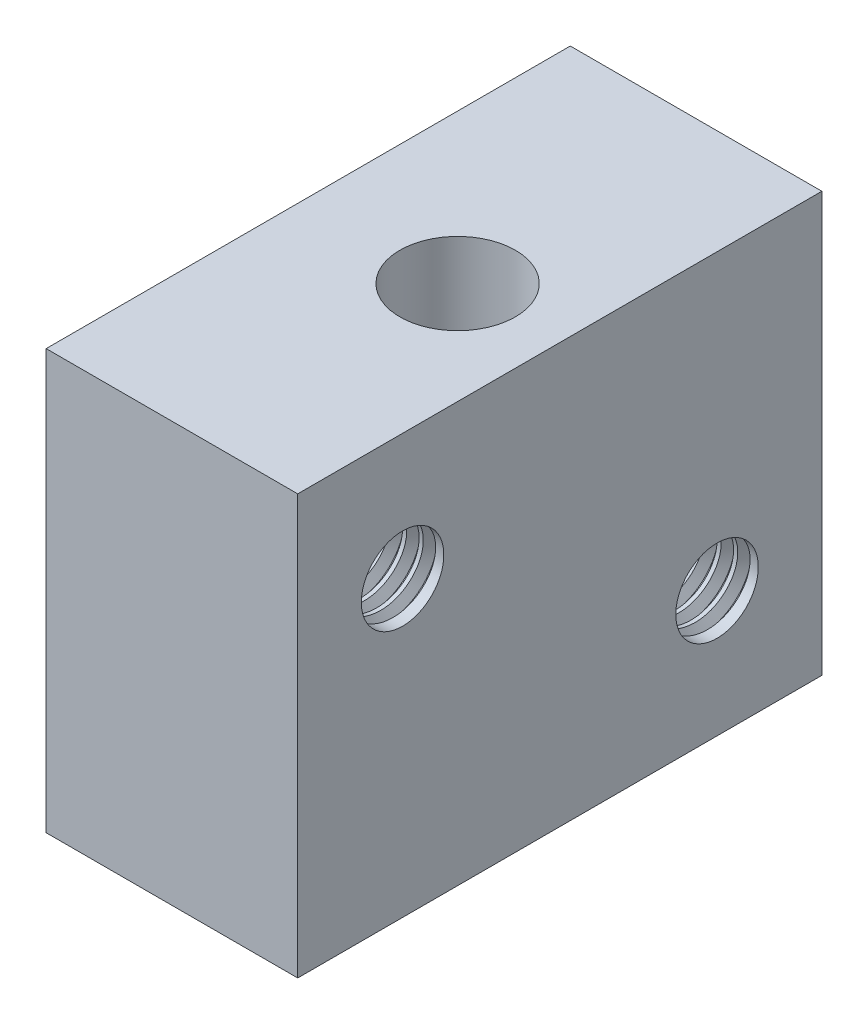
SolidWorks part; units mm, degrees
material "6061-T6 (SS)"
ref_plane "Front Plane" through (0, 0, 0) normal (1, 0, 0) x (0, 1, 0)
ref_plane "Top Plane" through (0, 0, 0) normal (0, 0, 1) x (0, 1, 0)
ref_plane "Right Plane" through (0, 0, 0) normal (0, 1, 0) x (-1, 0, 0)
sketch "Sketch1" plane through (0, 0, 0) normal (1, 0, 0) x (0, 1, 0)
  line L1 (6.35, -7.9375) -> (-6.35, -7.9375)
  line L2 (6.35, -7.9375) -> (6.35, 7.9375)
  line L3 (6.35, 7.9375) -> (-6.35, 7.9375)
  line L4 (-6.35, -7.9375) -> (-6.35, 7.9375)
  line L5 (6.35, -7.9375) -> (-6.35, 7.9375) construction
  line L6 (6.35, 7.9375) -> (-6.35, -7.9375) construction
  point P0 (0, 0)
  dimension "D1" = 15.875
  dimension "D2" = 12.7
extrude "Boss-Extrude1" add sketch "Sketch1" along normal blind 7.62
sketch "Sketch3" plane through (0, -6.35, 0) normal (0, -1, 0) x (1, 0, 0)
  line L10 (0, 7.9375) -> (0, -7.9375)
  line L11 (0, -7.9375) -> (7.62, -7.9375)
  line L12 (7.62, -7.9375) -> (7.62, 7.9375)
  line L13 (7.62, 7.9375) -> (0, 7.9375)
  line L14 (0, 7.9375) -> (0, -7.9375)
  line L15 (0, -7.9375) -> (7.62, -7.9375)
  line L16 (7.62, -7.9375) -> (7.62, 7.9375)
  line L17 (7.62, 7.9375) -> (0, 7.9375)
  circle A0 centre (4.525, 0) radius 1.75
  circle A1 centre (4.525, 0) radius 5 construction
  circle A2 centre (4.525, 0) radius 3 construction
  point P2 (9.525, 0)
  point P3 (2.775, 0)
  point P6 (-6.35, 0)
  dimension "D1" = 3.5
  dimension "D2" = 10
  dimension "D6" = 6
  dimension "D3" = 15.875
  dimension "D4" = 6.35
  dimension "D5" = 0
extrude "Cut-Extrude1" cut sketch "Sketch3" against normal blind 22.2885 contours A0 region at (4.525, -6.35, 0)
sketch "Sketch4" plane through (7.62, 0, 0) normal (1, 0, 0) x (0, 1, 0)
  line L0 (-6.35, 7.9375) -> (-6.35, -7.9375) construction
  line L1 (2.54, -4.7625) -> (-2.54, -4.7625) construction
  line L2 (2.54, -4.7625) -> (2.54, 4.7625) construction
  line L3 (2.54, 4.7625) -> (-2.54, 4.7625) construction
  line L4 (-2.54, -4.7625) -> (-2.54, 4.7625) construction
  line L5 (2.54, -4.7625) -> (-2.54, 4.7625) construction
  line L6 (2.54, 4.7625) -> (-2.54, -4.7625) construction
  line L7 (6.35, 7.9375) -> (-6.35, 7.9375) construction
  circle A3 centre (2.54, 4.7625) radius 1.25
  circle A4 centre (-2.54, -4.7625) radius 1.25
  point P0 (0, 0)
  dimension "D3" = 2.5
  dimension "D1" = 3.81
  dimension "D2" = 3.175
extrude "Cut-Extrude2" cut sketch "Sketch4" against normal blind 22.2885 contours A4 | A3 region at (7.62, 2.54, 4.7625) region at (7.62, -2.54, -4.7625)
thread "Thread2" pitch 0.5 method cut profile "Thread Profile2" start angle 0, offset 0, length 0, pitch 0.5, diameter 2.5
ref_plane "Plane2" through (7.62, 2.54, 6.0125) normal (0, -1, 0) x (0, 0, 1)
sketch "Thread Profile2" plane through (7.62, 2.54, 6.0125) normal (0, -1, 0) x (0, 0, 1)
  line L0 (0, 0) -> (0, 0.5) construction
  line L1 (0, 0) -> (0.2706, 0.1562)
  line L2 (0.2706, 0.1562) -> (0.2706, 0.2187)
  line L3 (0.2706, 0.2187) -> (0, 0.375)
  line L4 (0.2706, 0.1875) -> (0, 0.1875) construction
  line L11 (0, 0) -> (0, 0.375)
  point P2 (0, 0)
  dimension "Pitch" = 0.5
  dimension "Profile_Angle" = 60
  dimension "Profile_Land" = 0.0625
  dimension "Profile_Height" = 0.2706
thread "Thread3" pitch 0.5 method cut profile "Thread Profile3" start angle 0, offset 0, length 0, pitch 0.5, diameter 2.5
ref_plane "Plane3" through (7.62, -2.54, -3.5125) normal (0, -1, 0) x (0, 0, 1)
sketch "Thread Profile3" plane through (7.62, -2.54, -3.5125) normal (0, -1, 0) x (0, 0, 1)
  line L0 (0, 0) -> (0, 0.5) construction
  line L1 (0, 0) -> (0.2706, 0.1562)
  line L2 (0.2706, 0.1562) -> (0.2706, 0.2187)
  line L3 (0.2706, 0.2187) -> (0, 0.375)
  line L4 (0.2706, 0.1875) -> (0, 0.1875) construction
  line L11 (0, 0) -> (0, 0.375)
  point P2 (0, 0)
  dimension "Pitch" = 0.5
  dimension "Profile_Angle" = 60
  dimension "Profile_Land" = 0.0625
  dimension "Profile_Height" = 0.2706
